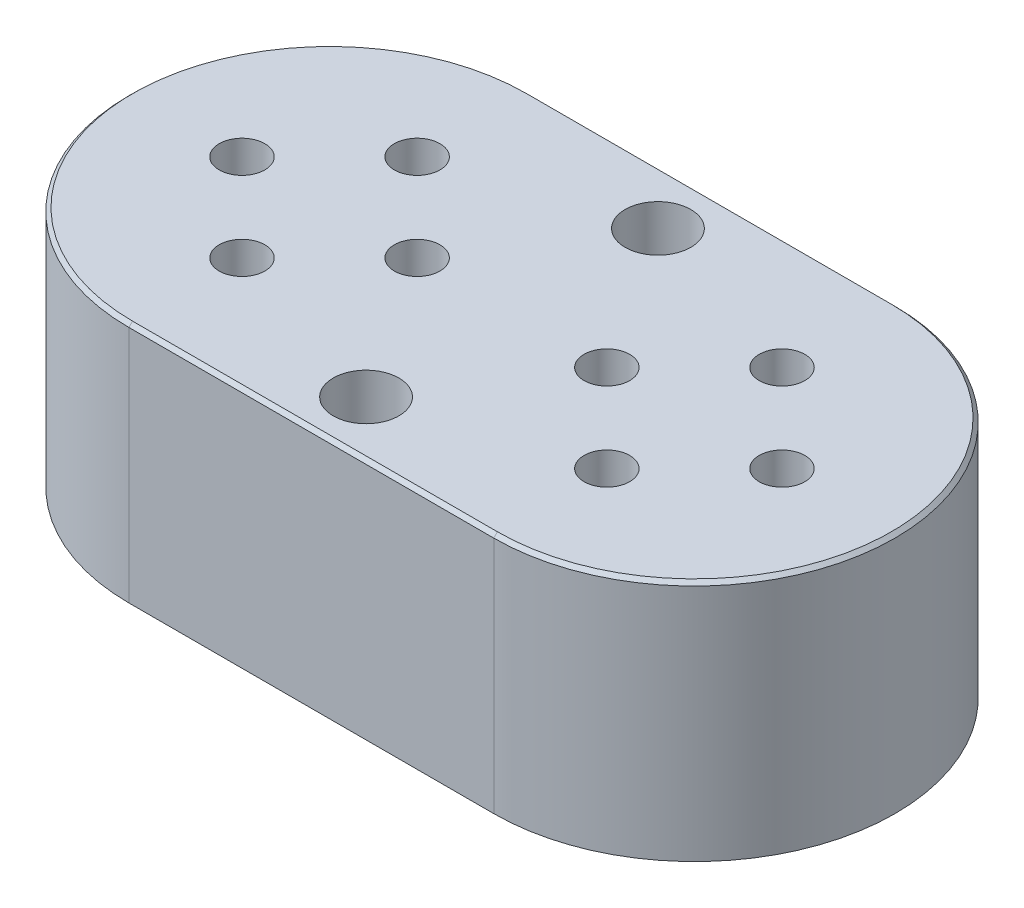
SolidWorks part; units mm, degrees
ref_plane "Front Plane" through (0, 0, 0) normal (0, 0, 1) x (1, 0, 0)
ref_plane "Top Plane" through (0, 0, 0) normal (0, 1, 0) x (1, 0, 0)
ref_plane "Right Plane" through (0, 0, 0) normal (1, 0, 0) x (0, 0, -1)
sketch "Sketch1" plane through (0, 0, 0) normal (0, 1, 0) x (1, 0, 0)
  line L0 (0, 0) -> (25.4, 0) construction
  line L1 (0, 13.97) -> (25.4, 13.97)
  line L2 (0, -13.97) -> (25.4, -13.97)
  arc A0 (0, 13.97) -> (0, -13.97) centre (0, 0) ccw
  arc A1 (25.4, -13.97) -> (25.4, 13.97) centre (25.4, 0) ccw
  point P3 (12.7, 0)
  dimension "D1" = 27.94
  dimension "D2" = 25.4
extrude "Boss-Extrude1" add sketch "Sketch1" along normal blind 16.8656
chamfer "Chamfer1" distance 0.254 angle 45 4 edges at (39.37, 16.8656, 0) (12.7, 16.8656, -13.97) (12.7, 16.8656, 13.97) (-13.97, 16.8656, 0)
sketch "Sketch3" plane through (0, 16.8656, 0) normal (0, 1, 0) x (1, 0, 0)
  line L0 (12.7, 13.716) -> (12.7, -13.716) construction
  line L1 (25.4, 13.716) -> (0, 13.716) construction
  line L2 (0, -13.716) -> (25.4, -13.716) construction
  circle A0 centre (25.4, 0) radius 6.096 construction
  circle A1 centre (25.4, 6.096) radius 1.5875
  circle A2 centre (31.496, 0) radius 1.5875
  circle A3 centre (25.4, -6.096) radius 1.5875
  circle A4 centre (19.304, 0) radius 1.5875
  circle A5 centre (-6.096, 0) radius 1.5875
  circle A6 centre (0, 0) radius 6.096 construction
  circle A7 centre (6.096, 0) radius 1.5875
  circle A8 centre (0, -6.096) radius 1.5875
  circle A9 centre (0, 6.096) radius 1.5875
  dimension "D1" = 12.192
  dimension "D2" = 3.175
extrude "Cut-Extrude1" cut sketch "Sketch3" against normal blind 16.3576
sketch "Sketch4" plane through (0, 16.8656, 0) normal (0, 1, 0) x (1, 0, 0)
  line L0 (0, 13.97) -> (25.4, 13.97) construction
  line L1 (-12.2403, 0) -> (39.116, 0) construction
  circle A1 centre (12.7, 10.16) radius 2.286
  arc A2 (25.4, -13.716) -> (25.4, 13.716) centre (25.4, 0) ccw construction
  circle A3 centre (12.7, -10.16) radius 2.286
  dimension "D1" = 3.81
extrude "Cut-Extrude2" cut sketch "Sketch4" against normal through all
ref_plane "Plane1" through (12.7, 0, 0) normal (1, 0, 0) x (0, 0, -1)
ref_axis "Axis1" through (25.4, 16.6116, 0) along (0, -1, 0)
ref_axis "Axis2" through (0, 16.6116, 0) along (0, -1, 0)
